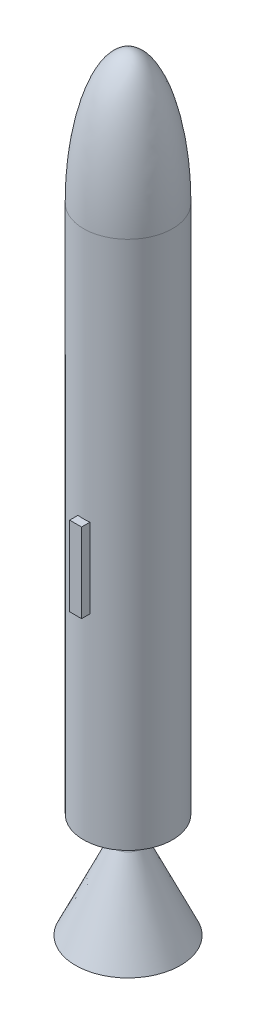
SolidWorks part; units mm, degrees
other "Boosters"
ref_plane "Front Plane" through (0, 0, 0) normal (0, 0, 1) x (1, 0, 0)
ref_plane "Top Plane" through (0, 0, 0) normal (0, 1, 0) x (1, 0, 0)
ref_plane "Right Plane" through (0, 0, 0) normal (1, 0, 0) x (0, 0, -1)
sketch "Sketch1" plane through (0, 0, 0) normal (0, 0, 1) x (1, 0, 0)
  line L1 (0, 0) -> (56, 0)
  line L2 (0, 0) -> (0, -666.6)
  line L3 (0, -666.6) -> (56, -666.6)
  line L4 (56, 0) -> (56, -666.6)
  dimension "D1" = 56
  dimension "D2" = 666.6
revolve "Revolve1" add sketch "Sketch1" angle 360 about L2
dome "Dome1" faces to dome 1 distance 166.665 reverse direction no elliptical dome yes face at (-56, 0, 0) parameters "D1"=166.665
sketch "Sketch2" plane through (0, 0, 0) normal (0, 0, 1) x (1, 0, 0)
  line L0 (0, -1354.2673) -> (0, 0) construction
  line L1 (19.4053, -666.6) -> (19.0192, -667.2686)
  line L2 (-56, -666.6) -> (56, -666.6) construction
  line L3 (15, -682.2686) -> (15, -682.5793)
  line L4 (17.8108, -695.2579) -> (66, -798.6)
  line L5 (19.4053, -666.6) -> (0, -666.6)
  line L6 (0, -666.6) -> (0, -798.6)
  line L7 (0, -798.6) -> (66, -798.6)
  arc A0 (15, -682.5793) -> (17.8108, -695.2579) centre (45, -682.5793) ccw
  arc A1 (19.0192, -667.2686) -> (15, -682.2686) centre (45, -682.2686) ccw
  point P4 (0, -677.1337)
  point P14 (15, -689.2301)
  point P17 (15, -674.2301)
  dimension "D7" = 30
  dimension "D1" = 15
  dimension "D2" = 132
  dimension "D3" = 65
  dimension "D4" = 15
  dimension "D5" = 30
  dimension "D6" = 66
revolve "Revolve2" add sketch "Sketch2" angle 360 about L0
sketch "Sketch3" plane through (0, 0, 0) normal (0, 0, 1) x (1, 0, 0)
  line L0 (-56, -666.6) -> (56, -666.6) construction
  line L1 (-7.5, -416.6) -> (7.5, -416.6)
  line L2 (-7.5, -416.6) -> (-7.5, -316.6)
  line L3 (-7.5, -316.6) -> (7.5, -316.6)
  line L4 (7.5, -416.6) -> (7.5, -316.6)
  line L5 (-7.5, -416.6) -> (7.5, -316.6) construction
  line L6 (-7.5, -316.6) -> (7.5, -416.6) construction
  point P0 (0, -366.6)
  dimension "D1" = 300
  dimension "D2" = 100
  dimension "D3" = 15
extrude "Boss-Extrude1" add sketch "Sketch3" along normal blind 66
